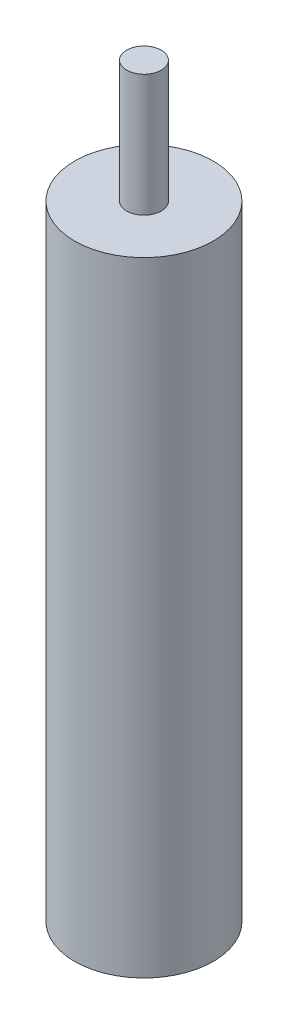
SolidWorks part; units mm, degrees
ref_plane "Front Plane" through (0, 0, 0) normal (0, 0, 1) x (1, 0, 0)
ref_plane "Top Plane" through (0, 0, 0) normal (0, 1, 0) x (1, 0, 0)
ref_plane "Right Plane" through (0, 0, 0) normal (1, 0, 0) x (0, 0, -1)
sketch "Sketch1" plane through (0, 0, 0) normal (0, 1, 0) x (1, 0, 0)
  circle A0 centre (0, 0) radius 12.7
  dimension "D1" = 25.4
extrude "Boss-Extrude1" add sketch "Sketch1" along normal blind 114.3
sketch "Sketch2" plane through (0, 114.3, 0) normal (0, 1, 0) x (1, 0, 0)
  circle A0 centre (0, 0) radius 3.175
  dimension "D1" = 6.35
extrude "Boss-Extrude2" add sketch "Sketch2" along normal blind 22.352
sketch "Sketch3" plane through (0, 136.652, 0) normal (0, 1, 0) x (1, 0, 0)
  point P0 (0, 0)
